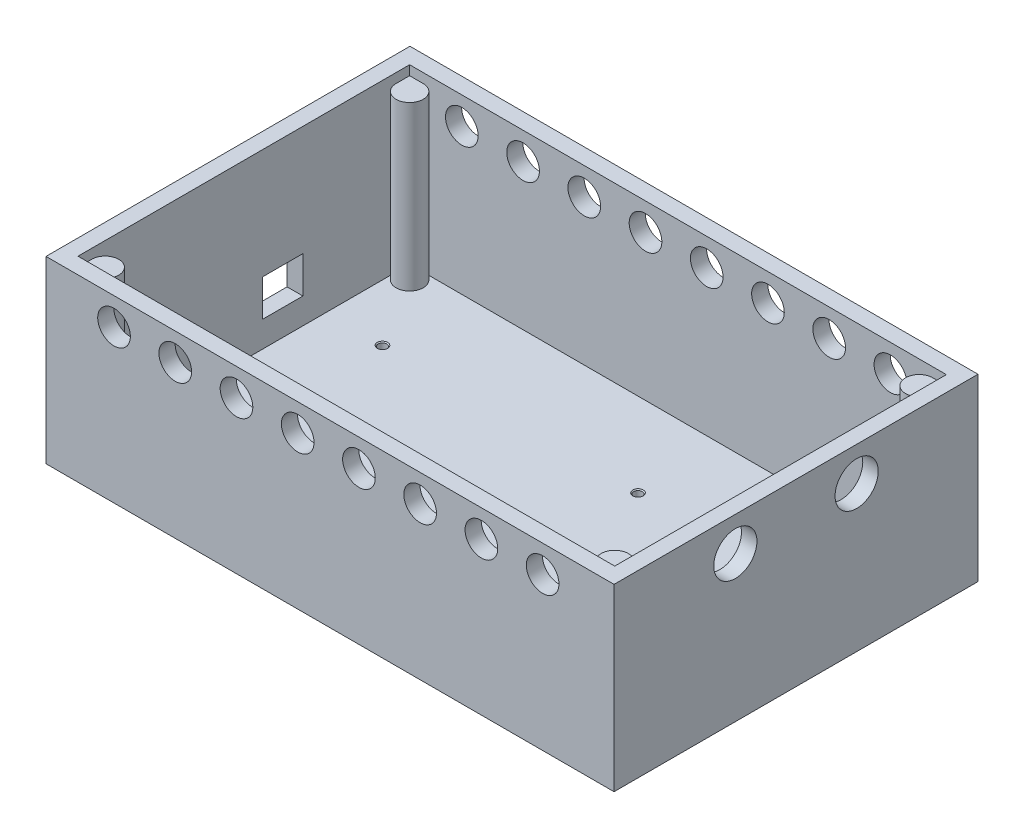
SolidWorks part; units mm, degrees
ref_plane "Front Plane" through (0, 0, 0) normal (0, 0, 1) x (1, 0, 0)
ref_plane "Top Plane" through (0, 0, 0) normal (0, 1, 0) x (1, 0, 0)
ref_plane "Right Plane" through (0, 0, 0) normal (1, 0, 0) x (0, 0, -1)
sketch "Sketch1" plane through (0, 0, 0) normal (0, 1, 0) x (1, 0, 0)
  line L1 (-96.1904, 42.7889) -> (70.8096, 42.7889)
  line L2 (-96.1904, 42.7889) -> (-96.1904, -64.2111)
  line L3 (-96.1904, -64.2111) -> (70.8096, -64.2111)
  line L4 (70.8096, 42.7889) -> (70.8096, -64.2111)
  dimension "D1" = 167
  dimension "D2" = 107
  dimension "D3" = 70.8096
  dimension "D4" = 42.7889
extrude "Boss-Extrude1" add sketch "Sketch1" along normal blind 52.8
sketch "Sketch2" plane through (0, 52.8, 0) normal (0, 1, 0) x (1, 0, 0)
  line L0 (-96.1904, 42.7889) -> (-96.1904, -64.2111) construction
  line L1 (-91.5404, 38.0389) -> (66.2596, 38.0389)
  line L2 (-91.5404, 38.0389) -> (-91.5404, -59.4611)
  line L3 (-91.5404, -59.4611) -> (66.2596, -59.4611)
  line L4 (66.2596, 38.0389) -> (66.2596, -59.4611)
  line L5 (70.8096, 42.7889) -> (-96.1904, 42.7889) construction
  dimension "D1" = 157.8
  dimension "D2" = 97.5
  dimension "D3" = 4.65
  dimension "D4" = 4.75
extrude "Cut-Extrude1" cut sketch "Sketch2" against normal blind 50.8
sketch "Sketch3" plane through (0, 0, 64.2111) normal (0, 0, 1) x (1, 0, 0)
  line L0 (-96.1904, 52.8) -> (70.8096, 52.8) construction
  line L1 (-96.1904, 52.8) -> (-96.1904, 0) construction
  circle A0 centre (-76.1904, 44.8) radius 4.8
  dimension "D1" = 9.6
  dimension "D2" = 8
  dimension "D3" = 20
extrude "Cut-Extrude2" cut sketch "Sketch3" against normal through all
pattern_linear "LPattern1" count 8 spacing 18 along (1, 0, 0) of "Cut-Extrude2"
sketch "Sketch4" plane through (70.8096, 0, 0) normal (1, 0, 0) x (0, 0, -1)
  line L0 (-64.2111, 52.8) -> (42.7889, 52.8) construction
  line L1 (-64.2111, 52.8) -> (-64.2111, 0) construction
  circle A0 centre (-28.5511, 42.8) radius 6.35
  dimension "D1" = 12.7
  dimension "D2" = 10
  dimension "D3" = 35.66
extrude "Cut-Extrude3" cut sketch "Sketch4" against normal up to next
pattern_linear "LPattern2" count 2 spacing 35.66 along (0, 0, -1) of "Cut-Extrude3"
sketch "Sketch5" plane through (-96.1904, 0, 0) normal (-1, 0, 0) x (0, 0, 1)
  line L1 (-6.6689, 20.4) -> (5.2711, 20.4)
  line L2 (-6.6689, 20.4) -> (-6.6689, 9.6)
  line L3 (-6.6689, 9.6) -> (5.2711, 9.6)
  line L4 (5.2711, 20.4) -> (5.2711, 9.6)
  line L5 (-42.7889, 0) -> (64.2111, 0) construction
  line L6 (64.2111, 52.8) -> (64.2111, 0) construction
  dimension "D1" = 11.94
  dimension "D2" = 10.8
  dimension "D3" = 20.4
  dimension "D4" = 58.94
extrude "Cut-Extrude4" cut sketch "Sketch5" against normal up to next
sketch "Sketch6" plane through (0, 2, 0) normal (0, 1, 0) x (1, 0, 0)
  line L0 (66.2596, -59.4611) -> (66.2596, 38.0389) construction
  line L1 (66.2596, 38.0389) -> (-91.5404, 38.0389) construction
  line L2 (66.2596, -10.7111) -> (-91.5404, -10.7111) construction
  line L3 (-91.5404, 38.0389) -> (-91.5404, -59.4611) construction
  line L4 (-12.6404, -59.4611) -> (-12.6404, 38.0389) construction
  line L5 (-91.5404, -59.4611) -> (66.2596, -59.4611) construction
  line L6 (66.2596, 34.0389) -> (66.2596, 38.0389)
  line L7 (66.2596, 38.0389) -> (62.2596, 38.0389)
  line L8 (66.2596, -59.4611) -> (62.2596, -59.4611)
  line L9 (66.2596, -55.4611) -> (66.2596, -59.4611)
  line L10 (-91.5404, 38.0389) -> (-87.5404, 38.0389)
  line L11 (-91.5404, 34.0389) -> (-91.5404, 38.0389)
  line L12 (-91.5404, -55.4611) -> (-91.5404, -59.4611)
  line L13 (-91.5404, -59.4611) -> (-87.5404, -59.4611)
  arc A0 (62.2596, 38.0389) -> (66.2596, 34.0389) centre (62.2596, 34.0389) ccw
  arc A1 (62.2596, -59.4611) -> (66.2596, -55.4611) centre (62.2596, -55.4611) cw
  arc A2 (-87.5404, 38.0389) -> (-91.5404, 34.0389) centre (-87.5404, 34.0389) cw
  arc A3 (-87.5404, -59.4611) -> (-91.5404, -55.4611) centre (-87.5404, -55.4611) ccw
  dimension "D1" = 8
extrude "Boss-Extrude5" add sketch "Sketch6" along normal blind 48
hole_wizard "M3 Tapped Hole1" positions "Sketch7" profile "Sketch8" tap size "M3" standard "ISO" end condition through all
sketch "Sketch7" plane through (-49.0204, 2, -140.9448) normal (0, 1, 0) x (1, 0, 0)
  point P0 (56.7696, -175.8812)
  point P3 (25.7689, -171.0027)
  point P6 (-25.8566, -175.8812)
  point P9 (-25.8566, -127.545)
  point P12 (49.2766, -127.545)
sketch "Sketch8" plane through (7.7492, 2, 34.9363) normal (1, 0, 0) x (0, 0, 1)
  line L0 (0, 0) -> (0, 2)
  line L1 (0, 2) -> (1.25, 2)
  line L2 (1.25, 2) -> (1.25, 0.275)
  line L3 (1.25, 0.275) -> (1.525, 0)
  line L4 (1.525, 0) -> (0, 0)
  line L5 (-1.25, 0.275) -> (-1.525, 0) construction
  line L6 (0, -6.35) -> (0, 107.95) construction
  dimension "Thru Tap Drill Dia." = 2.5
  dimension "Thru Tap Drill Depth" = 2
  dimension "Near C'Sink Dia." = 3.05
  dimension "Near C'Sink Angle" = 90
cosmetic thread "Hole Thread1" parameters "D2"=3
cosmetic thread "Hole Thread2" parameters "D2"=3
cosmetic thread "Hole Thread3" parameters "D2"=3
cosmetic thread "Hole Thread4" parameters "D2"=3
cosmetic thread "Hole Thread5" parameters "D2"=3
